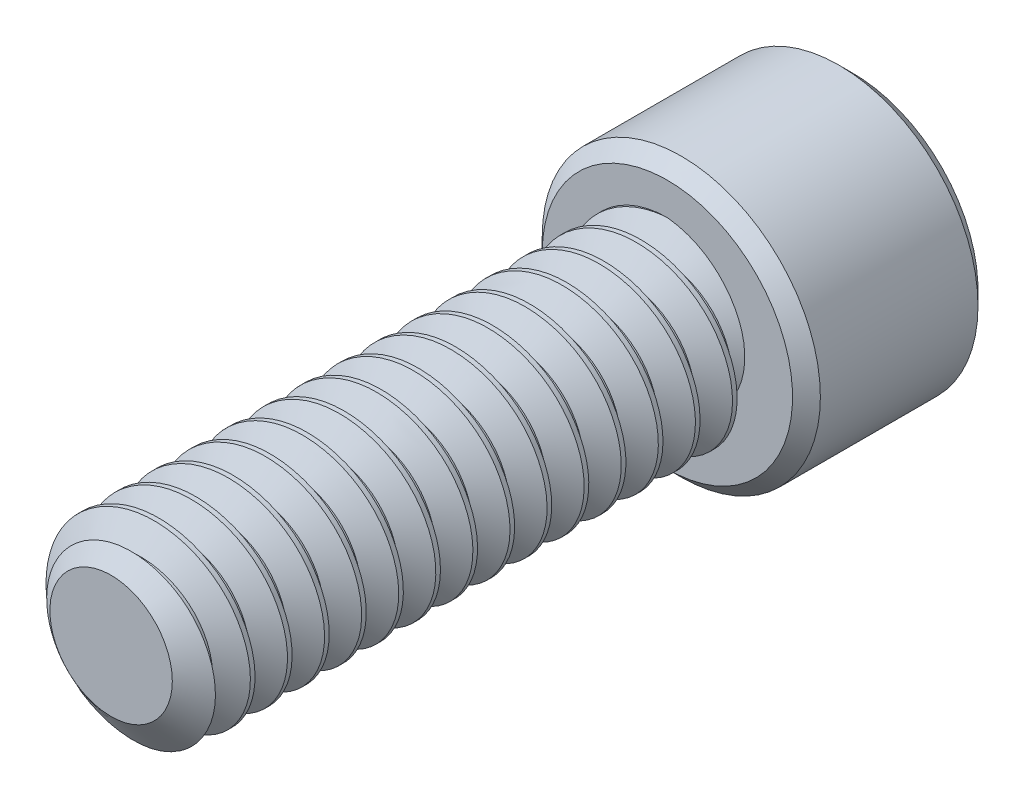
SolidWorks part; units mm, degrees
other "DetailItem1"
ref_plane "Front Plane" through (0, 0, 0) normal (0, 0, 1) x (1, 0, 0)
ref_plane "Top Plane" through (0, 0, 0) normal (0, 1, 0) x (1, 0, 0)
ref_plane "Right Plane" through (0, 0, 0) normal (1, 0, 0) x (0, 0, -1)
sketch "Sketch1" plane through (0, 0, 0) normal (0, 0, 1) x (1, 0, 0)
  circle A0 centre (0, 0) radius 3.175
  dimension "OD" = 6.35
extrude "Extrude1" add sketch "Sketch1" against normal blind 19.05
sketch "Sketch2" plane through (0, 0, 0) normal (0, 0, 1) x (1, 0, 0)
  circle A0 centre (0, 0) radius 3.175 construction
  circle A1 centre (0, 0) radius 3.175
curve "Helix/Spiral1" pitch 1.27 height 20.32 turns 16 parameters "pitch"=1.27
sketch "Sketch3" plane through (0, 0, 0) normal (1, 0, 0) x (0, 0, -1)
  line L0 (-1.1112, 3.175) -> (-0.635, 2.3501)
  line L1 (-0.635, 2.3501) -> (-0.4763, 2.3501)
  line L2 (-0.4763, 2.3501) -> (0, 3.175)
  line L3 (-1.1112, 3.175) -> (0, 3.175)
  line L4 (-0.5556, 3.175) -> (-0.5556, 2.3501) construction
  line L5 (-0.8731, 2.7626) -> (-0.2381, 2.7626) construction
  line L6 (0, 3.175) -> (0, -3.175) construction
  dimension "D1" = 0.1588
  dimension "D2" = 0.635
  dimension "D3" = 60
sweep "Cut-Sweep1" cut profiles "Sketch3" path "Helix/Spiral1"
sketch "Sketch4" plane through (0, 0, 0) normal (1, 0, 0) x (0, 0, -1)
  line L0 (0.7554, 3.175) -> (0, 2.0961)
  line L1 (0, 2.0961) -> (0, 3.175)
  line L2 (0.7554, 3.175) -> (0, 3.175)
  line L3 (-1.1112, 3.175) -> (0, 3.175) construction
  line L4 (0, 0) -> (7.0209, 0) construction
  dimension "D1" = 55
  dimension "D2" = 0.254
revolve "Cut-Revolve1" cut sketch "Sketch4" angle 360 about L4
sketch "Sketch6" plane through (0, 0, -19.05) normal (0, 0, -1) x (-1, 0, 0)
  circle A0 centre (0, 0) radius 4.7625
  dimension "head dia" = 9.525
extrude "Extrude2" add sketch "Sketch6" along normal blind 6.35
sketch "Sketch7" plane through (0, 0, -25.4) normal (0, 0, -1) x (-1, 0, 0)
  line L1 (0, 2.7496) -> (-2.3813, 1.3748)
  line L2 (-2.3813, 1.3748) -> (-2.3813, -1.3748)
  line L3 (-2.3813, -1.3748) -> (0, -2.7496)
  line L4 (0, -2.7496) -> (2.3813, -1.3748)
  line L5 (2.3813, -1.3748) -> (2.3813, 1.3748)
  line L6 (2.3813, 1.3748) -> (0, 2.7496)
  circle A0 centre (0, 0) radius 2.3813 construction
  dimension "hex dia" = 4.7625
extrude "Cut-Extrude1" cut sketch "Sketch7" against normal blind 3.5719
sketch "Sketch8" plane through (0, 0, -25.4) normal (0, 0, -1) x (-1, 0, 0)
  circle A0 centre (0, 0) radius 2.7496
extrude "Cut-Extrude2" cut sketch "Sketch8" against normal through all draft 45
chamfer "Chamfer1" distance 0.4763 angle 45 2 edges at (-4.7625, 0, -25.4) (-4.7625, 0, -19.05)
sketch "Sketch10" plane through (0, 0, -19.05) normal (0, 0, 1) x (1, 0, 0)
  circle A0 centre (0, 0) radius 3.175
extrude "Partial Thread" [suppressed] add sketch "Sketch10" along normal offset from surface (25.4 mm away) 22.225
sketch "Sketch9" plane through (0, 0, 0) normal (1, 0, 0) x (0, 0, -1)
  line L0 (0, 3.175) -> (0, -3.175) construction
  line L1 (1.905, 3.175) -> (1.905, -3.175) construction
  dimension "D1" = 1.905
equation "\"D3@Helix/Spiral1\" = \"screw length@Extrude1\"+\"pitch@Helix/Spiral1\""
equation "\"D1@Sketch3\" = \"pitch@Helix/Spiral1\"*.125"
equation "\"D2@Sketch3\" = \"pitch@Helix/Spiral1\"*.5"
equation "\"D1@Cut-Extrude1\" = \"hex dia@Sketch7\"*.75"
equation "\"D1@Chamfer1\" = \"head dia@Sketch6\"*.05"
equation "\"D1@Sketch9\" = \"pitch@Helix/Spiral1\"*1.5"
